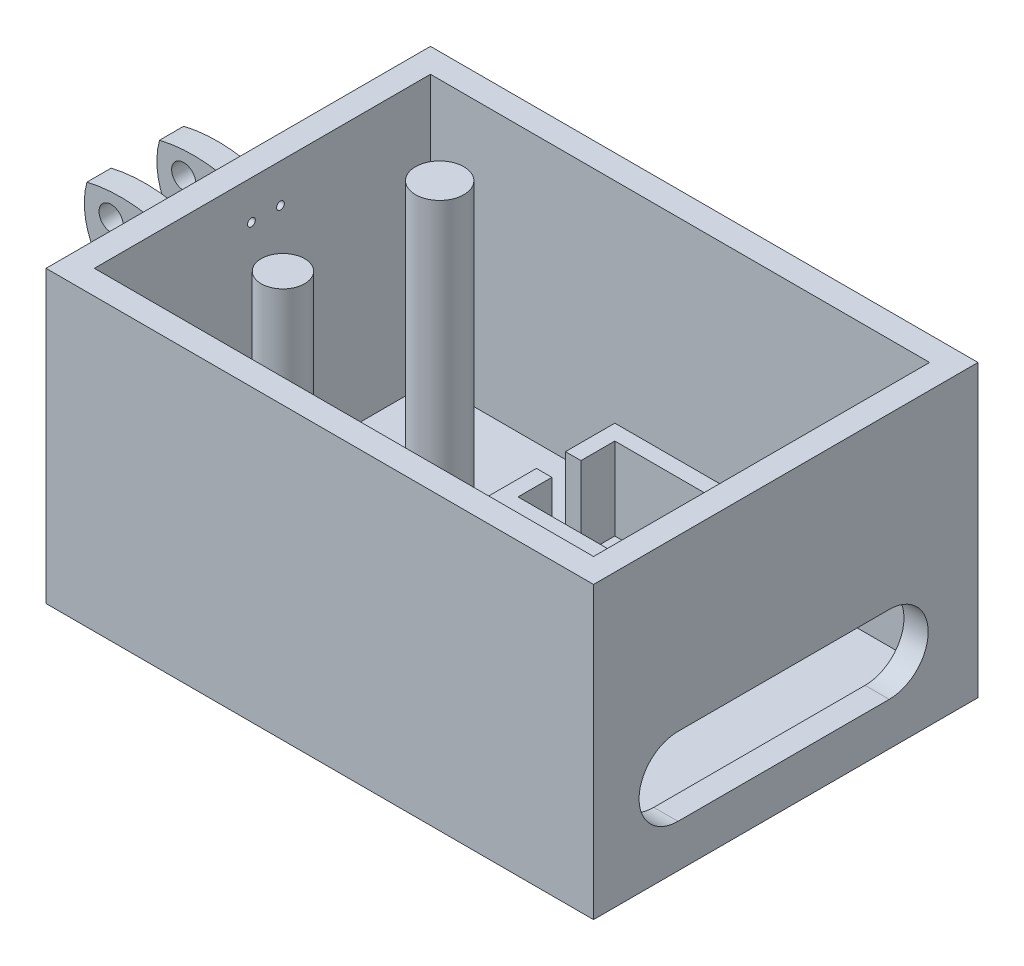
SolidWorks part; units mm, degrees
ref_plane "Front Plane" through (0, 0, 0) normal (0, 0, 1) x (1, 0, 0)
ref_plane "Top Plane" through (0, 0, 0) normal (0, 1, 0) x (1, 0, 0)
ref_plane "Right Plane" through (0, 0, 0) normal (1, 0, 0) x (0, 0, -1)
ref_plane "Palm Side Plane" through (0, 38.1, 0) normal (0, 1, 0) x (1, 0, 0)
ref_plane "Left Side Plane" through (0, 0, 63.5) normal (0, 0, 1) x (1, 0, 0)
ref_plane "Top Side Plane" through (-69.85, 0, 0) normal (1, 0, 0) x (0, 0, -1)
ref_plane "Wrist Plane" through (62.9138, 0, 0) normal (1, 0, 0) x (0, 0, -1)
sketch "Hand Direction Arrow" plane through (0, 38.1, 0) normal (0, 1, 0) x (1, 0, 0)
  line L0 (49.8191, -114.0829) -> (-36.738, -114.0829) construction
  line L1 (-36.738, -114.0829) -> (-22.4792, -131.555) construction
  line L2 (-36.738, -114.0829) -> (-22.4792, -99.8241) construction
sketch "Sketch2" plane through (0, 0, 0) normal (0, 1, 0) x (1, 0, 0)
  line L5 (-69.85, -63.5) -> (69.85, 63.5) construction
  line L6 (-69.85, 63.5) -> (69.85, -63.5) construction
  line L7 (-20.7784, 52.7587) -> (-36.189, 52.7587)
  line L8 (-36.189, 52.7587) -> (-36.189, 33.7087)
  line L16 (-38.8642, 27.3587) -> (-36.189, 33.7087)
  line L19 (15.3118, -63.2103) -> (-3.7382, -63.2103)
  line L20 (-3.7382, -63.2103) -> (-3.7382, -58.593)
  line L21 (22.9098, -62.5249) -> (22.9098, 48.896)
  line L22 (-48.9477, 8.3087) -> (-48.9477, 27.3587)
  line L23 (-48.9477, 27.3587) -> (-38.8642, 27.3587)
  line L24 (-48.9477, 8.3087) -> (-48.9477, -42.4913)
  line L25 (-42.9594, -42.4913) -> (-48.9477, -42.4913)
  arc A0 (22.9098, 48.896) -> (-20.7784, 52.7587) centre (-16.6219, -149.2259) ccw
  arc A2 (-42.9594, -42.4913) -> (-16.4221, -49.7553) centre (-56.8306, -145.2734) cw
  arc A5 (-3.7382, -58.593) -> (-16.4221, -49.7553) centre (16.7508, -15.6666) cw
  arc A6 (15.3118, -63.2103) -> (22.9098, -62.5249) centre (14.5642, -12.4678) ccw
  point P0 (0, 0)
  dimension "D1" = 19.05
  dimension "D4" = 19.05
  dimension "D5" = 19.05
  dimension "D6" = 6.35
extrude "Boss-Extrude1" add sketch "Sketch2" along normal blind 38.1
sketch "Sketch3" plane through (0, 38.1, 0) normal (0, 1, 0) x (1, 0, 0)
  line L5 (-45.7727, 24.1837) -> (19.7348, 24.1837)
  line L6 (22.9098, -62.5249) -> (22.9098, 48.896) construction
  line L24 (-45.7727, 7.713) -> (-45.7727, 24.1837)
  line L26 (-48.9477, 27.3587) -> (-48.9477, -42.4913) construction
  line L41 (-38.8642, 27.3587) -> (22.9098, 27.3587)
  line L42 (-45.7727, 7.713) -> (-45.7727, -19.9216)
  line L44 (-45.7727, -19.9216) -> (19.7348, -19.9216)
  line L45 (19.7348, -19.9216) -> (19.7348, 24.1837)
  line L46 (-48.9477, -23.0966) -> (22.9098, -23.0966)
  line L47 (-48.9477, -55.2233) -> (-48.9477, -23.0966)
  line L48 (-48.9477, 27.3587) -> (-48.9477, -42.4913) construction
  arc A7 (-48.9477, -55.2233) -> (22.9098, -23.0966) centre (8.6461, -87.618) ccw
  arc A11 (-38.8642, 27.3587) -> (22.9098, 27.3587) centre (-7.9772, 76.0331) cw
  point P0 (0, 0)
  point P6 (-45.5127, -25.7954)
  point P15 (-48.9477, -27.2263)
  point P29 (-45.5127, -25.7954)
  dimension "D2" = 3.175
  dimension "D3" = 3.175
  dimension "D4" = 3.175
  dimension "D11" = 3.175
extrude "Cut-Extrude1" cut sketch "Sketch3" against normal blind 34.925
sketch "Sketch6" plane through (0, 0, 0) normal (0, 1, 0) x (1, 0, 0)
  line L0 (-18.154, -9.4667) -> (-16.122, -9.4667)
  line L7 (8.008, -13.9117) -> (-16.122, -13.9117)
  line L8 (8.008, -13.9117) -> (8.008, -9.4667)
  line L9 (8.008, -1.2117) -> (-16.122, -1.2117)
  line L10 (-16.122, -13.9117) -> (-16.122, -9.4667)
  line L11 (8.008, -13.9117) -> (-16.122, -1.2117) construction
  line L12 (8.008, -1.2117) -> (-16.122, -13.9117) construction
  line L13 (10.04, -15.9437) -> (-18.154, -15.9437)
  line L14 (10.04, -15.9437) -> (10.04, -9.4667)
  line L15 (10.04, 0.8203) -> (-18.154, 0.8203)
  line L16 (-18.154, -15.9437) -> (-18.154, -9.4667)
  line L17 (10.04, -15.9437) -> (-18.154, 0.8203) construction
  line L18 (10.04, 0.8203) -> (-18.154, -15.9437) construction
  line L19 (-18.154, -5.6567) -> (-16.122, -5.6567)
  line L20 (-18.154, -5.6567) -> (-18.154, 0.8203)
  line L21 (-16.122, -5.6567) -> (-16.122, -1.2117)
  line L22 (8.008, -9.4667) -> (10.04, -9.4667)
  line L23 (8.008, -5.6567) -> (10.04, -5.6567)
  line L24 (8.008, -5.6567) -> (8.008, -1.2117)
  line L25 (10.04, -5.6567) -> (10.04, 0.8203)
  point P0 (26.0547, 16.5381)
  point P6 (-4.057, -7.5617)
  point P29 (-4.057, -7.5617)
  dimension "D6" = 2.032
  dimension "D7" = 2.032
  dimension "D9" = 12.7
  dimension "D10" = 24.13
  dimension "D11" = 4.445
  dimension "D12" = 4.445
  dimension "D13" = 4.445
  dimension "D14" = 4.445
extrude "Servo Box 1" add sketch "Sketch6" along normal blind 13.97
sketch "Sketch7" plane through (0, 0, 0) normal (0, 1, 0) x (1, 0, 0)
  line L0 (-18.154, 10.4723) -> (-16.122, 10.4723)
  line L5 (10.04, 0.8203) -> (-18.154, 0.8203) construction
  line L6 (-18.154, 0.8203) -> (-18.154, -5.6567) construction
  line L7 (8.008, 6.0273) -> (-16.122, 6.0273)
  line L8 (8.008, 6.0273) -> (8.008, 10.4723)
  line L9 (8.008, 18.7273) -> (-16.122, 18.7273)
  line L10 (-16.122, 6.0273) -> (-16.122, 10.4723)
  line L11 (8.008, 6.0273) -> (-16.122, 18.7273) construction
  line L12 (8.008, 18.7273) -> (-16.122, 6.0273) construction
  line L13 (10.04, 3.9953) -> (-18.154, 3.9953)
  line L14 (10.04, 3.9953) -> (10.04, 10.4723)
  line L15 (10.04, 20.7593) -> (-18.154, 20.7593)
  line L16 (-18.154, 3.9953) -> (-18.154, 10.4723)
  line L17 (10.04, 3.9953) -> (-18.154, 20.7593) construction
  line L18 (10.04, 20.7593) -> (-18.154, 3.9953) construction
  line L19 (-18.154, 14.2823) -> (-16.122, 14.2823)
  line L20 (-18.154, 14.2823) -> (-18.154, 20.7593)
  line L21 (-16.122, 14.2823) -> (-16.122, 18.7273)
  line L22 (8.008, 10.4723) -> (10.04, 10.4723)
  line L23 (8.008, 14.2823) -> (10.04, 14.2823)
  line L24 (8.008, 14.2823) -> (8.008, 18.7273)
  line L25 (10.04, 14.2823) -> (10.04, 20.7593)
  point P0 (-14.8998, -5.4903)
  point P6 (-4.057, 12.3773)
  point P29 (-4.057, 12.3773)
  dimension "D2" = 3.175
  dimension "D3" = 0
  dimension "D6" = 2.032
  dimension "D7" = 2.032
  dimension "D9" = 12.7
  dimension "D10" = 24.13
  dimension "D11" = 4.445
  dimension "D12" = 4.445
  dimension "D13" = 4.445
  dimension "D14" = 4.445
extrude "Servo Box 2" add sketch "Sketch7" along normal blind 13.97
ref_plane "Pinky Attachment Plane" through (0, 0, -52.7587) normal (0, 0, -1) x (-1, 0, 0)
ref_plane "Ring Attachment Plane" through (0, 0, -12.1187) normal (0, 0, -1) x (-1, 0, 0)
ref_plane "Middle Attachment Plane" through (0, 0, 13.2813) normal (0, 0, -1) x (-1, 0, 0)
ref_plane "Pointer Attachment Plane" through (0, 0, 38.6813) normal (0, 0, -1) x (-1, 0, 0)
ref_plane "Thumb Attachment Plane" through (-3.7382, 0, 0) normal (-1, 0, 0) x (0, 0, 1)
sketch "Sketch36" plane through (0, 0, -12.1187) normal (0, 0, -1) x (-1, 0, 0)
  line L3 (48.9477, 29.21) -> (48.9477, 18.0742)
  line L5 (48.9477, 18.0742) -> (53.3927, 18.0742)
  line L6 (53.3927, 38.1) -> (53.3927, 18.0742) construction
  line L7 (48.9477, 38.1) -> (48.9477, 0) construction
  line L8 (53.3927, 18.0742) -> (59.7427, 18.0742)
  line L9 (59.7427, 18.0742) -> (59.7427, 21.2492)
  line L10 (-22.9098, 38.1) -> (48.9477, 38.1) construction
  arc A0 (62.9177, 31.242) -> (59.7427, 21.2492) centre (53.6065, 28.6996) cw
  circle A1 centre (59.7427, 28.7074) radius 1.5875
  arc A2 (48.9477, 29.21) -> (62.9177, 31.242) centre (58.4796, 12.7162) cw
  dimension "D1" = 4.445
  dimension "D2" = 10.795
  dimension "D3" = 13.97
  dimension "D5" = 10.795
  dimension "D4" = 6.858
  dimension "D6" = 3.175
extrude "Ring Attachment" add sketch "Sketch36" against normal blind 19.05
sketch "Sketch40" plane through (0, 38.1, 0) normal (0, 1, 0) x (1, 0, 0)
  line L33 (-45.7727, 24.1837) -> (-45.7727, -19.9216) construction
  line L34 (-48.9477, -6.9313) -> (-48.9477, -3.7563)
  line L36 (-48.9477, -3.7563) -> (-65.3617, -3.7563)
  line L37 (-65.3617, -3.7563) -> (-65.3617, -0.5813)
  line L38 (-65.3617, -0.5813) -> (-48.9477, -0.5813)
  line L39 (-48.9477, -0.5813) -> (-48.9477, 5.7687)
  line L40 (-48.9477, 5.7687) -> (-65.7763, 5.7687)
  line L41 (-65.7763, 5.7687) -> (-65.7763, 8.9437)
  line L42 (-65.7763, 8.9437) -> (-48.9477, 8.9437)
  line L43 (-48.9477, 8.9437) -> (-48.9477, 12.1187)
  line L55 (-48.9477, 27.3587) -> (-48.9477, -23.0966) construction
  arc A5 (-48.9477, -6.9313) -> (-48.9477, 12.1187) centre (-63.2034, 2.5937) cw
  point P0 (0, 0)
  dimension "D11" = 3.175
  dimension "D19" = 3.175
  dimension "D20" = 3.175
  dimension "D22" = 3.175
  dimension "D24" = 3.175
extrude "Attachment Trim" cut sketch "Sketch40" against normal blind 25.4
sketch "Sketch33" plane through (-69.85, 0, 0) normal (1, 0, 0) x (0, 0, -1)
  line L1 (27.3587, 38.1) -> (-23.0966, 38.1) construction
  line L4 (8.9437, 18.0742) -> (8.9437, 29.21) construction
  circle A0 centre (0.6887, 33.02) radius 0.508
  circle A1 centre (4.4987, 33.02) radius 0.508
  dimension "D1" = 4.445
  dimension "D2" = 5.08
  dimension "D3" = 5.08
  dimension "D4" = 3.81
extrude "Ring Finger Holes" cut sketch "Sketch33" along normal blind 31.75
sketch "Sketch41" plane through (62.9138, 0, 0) normal (1, 0, 0) x (0, 0, -1)
  line L0 (-12.0167, 10.7439) -> (15.7102, 10.7439) construction
  line L1 (-12.0167, 15.8519) -> (15.7102, 15.8519)
  line L2 (-12.0167, 5.6359) -> (15.7102, 5.6359)
  arc A0 (-12.0167, 15.8519) -> (-12.0167, 5.6359) centre (-12.0167, 10.7439) ccw
  arc A1 (15.7102, 5.6359) -> (15.7102, 15.8519) centre (15.7102, 10.7439) ccw
  point P2 (1.8468, 10.7439)
  point P7 (-14.0484, 10.8634)
  point P8 (19.5346, 10.8634)
  point P9 (15.7102, 10.9829)
  point P10 (-12.0167, 10.7439)
extrude "Cord Hole" cut sketch "Sketch41" against normal blind 44.45
sketch "Band Reference Line (Fingers)" plane through (0, 0, 0) normal (0, 0, 1) x (1, 0, 0)
  line L0 (-36.189, 8.89) -> (-63.3567, 8.89) construction
  line L1 (-36.189, 3.175) -> (-36.189, 0) construction
  line L2 (-38.8642, 0) -> (-48.9477, 0) construction
  dimension "D1" = 8.89
sketch "Sketch52" plane through (0, 0, -12.1187) normal (0, 0, -1) x (-1, 0, 0)
  line L6 (52.0794, 6.5758) -> (48.9477, 6.7988)
  line L7 (48.9477, 6.7988) -> (48.9477, 3.6818)
  arc A10 (51.562, 4.8624) -> (48.9477, 3.6818) centre (51.9425, 0.535) ccw
  arc A11 (53.2594, 3.4933) -> (51.562, 4.8624) centre (51.2326, 2.7173) ccw
  arc A12 (51.8755, 1.7634) -> (53.2594, 3.4933) centre (51.1377, 3.7721) ccw
  arc A13 (51.2806, 2.6606) -> (51.8755, 1.7634) centre (51.8765, 2.4099) ccw
  arc A14 (50.0744, 2.3556) -> (51.2806, 2.6606) centre (50.6775, 2.5081) cw
  arc A15 (51.7195, 0.6123) -> (50.0744, 2.3556) centre (51.7196, 2.2603) cw
  arc A16 (54.7171, 4.061) -> (52.0794, 6.5758) centre (51.7621, 3.6024) ccw
  arc A17 (51.7195, 0.6123) -> (54.7171, 4.061) centre (51.7621, 3.6024) ccw
  point P0 (52.0794, 6.5758)
extrude "Ring Hook" add sketch "Sketch52" against normal blind 19.05
sketch "Sketch56" plane through (0, 0, 13.2813) normal (0, 0, -1) x (-1, 0, 0)
  line L4 (59.3076, 8.89) -> (56.7676, 8.89)
  line L6 (59.3076, 6.7988) -> (56.7676, 6.7988)
  line L7 (56.7676, 6.7988) -> (56.7676, 3.6818)
  line L8 (56.7676, 12.007) -> (56.7676, 8.89)
  arc A0 (59.3076, 14.3236) -> (62.0244, 11.6068) centre (59.3076, 11.6068) cw
  arc A1 (62.0244, 11.6068) -> (59.3076, 8.89) centre (59.3076, 11.6068) cw
  arc A2 (59.3076, 14.3236) -> (58.1015, 13.0471) centre (59.3428, 13.0823) ccw
  arc A3 (58.1015, 13.0471) -> (58.8022, 13.067) centre (58.4518, 13.057) ccw
  arc A4 (58.8022, 13.067) -> (59.3428, 13.6986) centre (59.4487, 13.0608) cw
  arc A5 (59.3428, 13.6986) -> (61.2287, 11.7836) centre (59.0992, 11.5725) cw
  arc A6 (61.2287, 11.7836) -> (59.3076, 9.9198) centre (59.0785, 12.0779) cw
  arc A7 (59.3076, 9.9198) -> (56.7676, 12.007) centre (60.5905, 14.0702) cw
  arc A10 (59.3076, 5.7689) -> (56.7676, 3.6818) centre (60.5905, 1.6186) ccw
  arc A11 (61.2287, 3.9052) -> (59.3076, 5.7689) centre (59.0785, 3.6108) ccw
  arc A12 (59.3428, 1.9902) -> (61.2287, 3.9052) centre (59.0992, 4.1162) ccw
  arc A13 (58.8022, 2.6218) -> (59.3428, 1.9902) centre (59.4487, 2.628) ccw
  arc A14 (58.1015, 2.6417) -> (58.8022, 2.6218) centre (58.4518, 2.6318) cw
  arc A15 (59.3076, 1.3652) -> (58.1015, 2.6417) centre (59.3428, 2.6065) cw
  arc A16 (62.0244, 4.082) -> (59.3076, 6.7988) centre (59.3076, 4.082) ccw
  arc A17 (59.3076, 1.3652) -> (62.0244, 4.082) centre (59.3076, 4.082) ccw
extrude "Middle Hook" add sketch "Sketch56" against normal blind 19.05 separate body
sketch "Sketch57" plane through (0, 0, 13.2813) normal (0, 0, -1) x (-1, 0, 0)
  line L1 (56.7676, 15.0568) -> (63.2114, 15.0568)
  line L2 (56.7676, 15.0568) -> (56.7676, 7.7531)
  line L3 (56.7676, 7.7531) -> (63.2114, 7.7531)
  line L4 (63.2114, 15.0568) -> (63.2114, 7.7531)
extrude "Middle Hook Cut 1" cut sketch "Sketch57" against normal blind 19.05
sketch "Band Reference Line (Thumb)" plane through (-3.7382, 0, 0) normal (-1, 0, 0) x (0, 0, 1)
  line L0 (58.593, 8.89) -> (76.2209, 8.89) construction
  line L1 (58.593, 3.175) -> (58.593, 0) construction
  line L2 (58.593, 0) -> (63.2103, 0) construction
  dimension "D1" = 8.89
sketch "Sketch65" plane through (0, 0, 0) normal (0, 1, 0) x (1, 0, 0)
  line L30 (-54.7525, 12.1187) -> (-54.7525, -6.9313) construction
  line L31 (-48.9477, 14.7165) -> (-54.7525, 14.7165)
  line L32 (-48.9477, 14.7165) -> (-48.9477, 5.1337)
  line L33 (-48.9477, 5.1337) -> (-54.7525, 5.1337)
  line L34 (-54.7525, 14.7165) -> (-54.7525, 5.1337)
  line L35 (-48.9477, -6.9313) -> (-48.9477, 12.1187) construction
  line L36 (-48.9477, 0.0537) -> (-54.7525, 0.0537)
  line L37 (-48.9477, 0.0537) -> (-48.9477, -6.9313)
  line L38 (-48.9477, -6.9313) -> (-54.7525, -6.9313)
  line L39 (-54.7525, 0.0537) -> (-54.7525, -6.9313)
  line L40 (-54.7525, -6.9313) -> (-51.7195, -6.9313) construction
  line L51 (-64.5731, -9.5782) -> (-54.2045, -9.5782)
  line L52 (-64.5731, -9.5782) -> (-64.5731, -36.4922)
  line L53 (-64.5731, -36.4922) -> (-54.2045, -36.4922)
  line L54 (-54.2045, -9.5782) -> (-54.2045, -36.4922)
  dimension "D7" = 5.08
  dimension "D8" = 6.985
extrude "Cut-Extrude9" cut sketch "Sketch65" along normal blind 15.24
sketch "Sketch66" plane through (0, 38.1, 0) normal (0, 1, 0) x (1, 0, 0)
  line L1 (-48.9477, -23.0966) -> (22.9098, -23.0966)
  line L3 (22.9098, 27.3587) -> (-48.9477, 27.3587)
  arc A0 (-48.9477, -23.0966) -> (22.9098, -23.0966) centre (-13.0189, -114.3663) ccw
  arc A1 (-48.9477, 27.3587) -> (22.9098, 27.3587) centre (-13.0189, 70.2201) cw
  point P12 (-48.9477, 8.3087)
  point P13 (-48.9477, 8.3087)
  point P14 (0, 0)
extrude "Cut-Extrude10" cut sketch "Sketch66" against normal blind 50.8
sketch "Sketch67" plane through (0, 38.1, 0) normal (0, 1, 0) x (1, 0, 0)
  line L0 (-16.122, -9.4667) -> (-18.154, -9.4667) construction
  line L1 (-18.154, 14.2823) -> (-16.122, 14.2823) construction
  line L2 (-45.7727, 24.1837) -> (-45.7727, -19.9216) construction
  line L3 (-45.7727, 24.1837) -> (-45.7727, -19.9216) construction
  circle A0 centre (-33.0727, -7.8792) radius 2.849
  circle A1 centre (-33.0727, 12.6948) radius 3.175
  point P6 (0, 0)
  point P11 (0, 0)
  dimension "D1" = 1.5875
  dimension "D2" = 1.5875
  dimension "D3" = 12.7
  dimension "D4" = 12.7
extrude "Boss-Extrude2" add sketch "Sketch67" against normal blind 38.1
